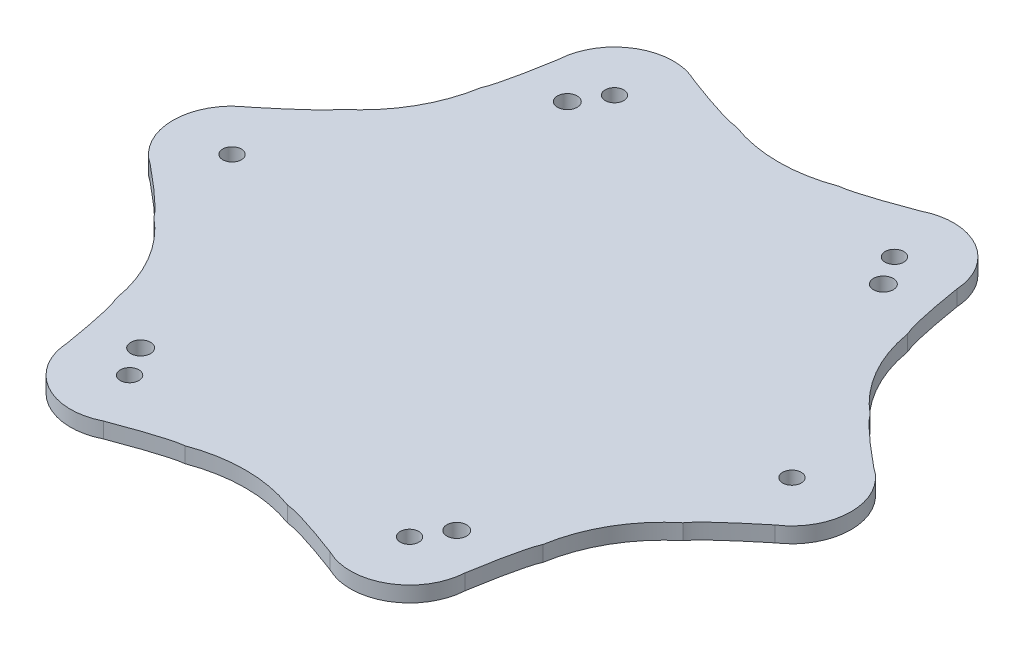
SolidWorks part; units mm, degrees
material "ABS"
ref_plane "Front" through (0, 0, 0) normal (0, 0, 1) x (1, 0, 0)
ref_plane "Top" through (0, 0, 0) normal (0, 1, 0) x (1, 0, 0)
ref_plane "Right" through (0, 0, 0) normal (1, 0, 0) x (0, 0, -1)
sketch "Sketch1" plane through (0, 0, 0) normal (0, 1, 0) x (1, 0, 0)
  line L0 (0, 45) -> (0, -45) construction
  line L1 (-45, 0) -> (45, 0) construction
  line L10 (0, 45) -> (0, 37.5) construction
  circle A0 centre (0, 0) radius 45
  dimension "D6" = 90
extrude "Boss-Extrude2" add sketch "Sketch1" along normal blind 2.5
ref_plane "Plane1" through (0, 2.5, 0) normal (0, 1, 0) x (1, 0, 0)
sketch "Sketch2" plane through (0, 2.5, 0) normal (0, 1, 0) x (1, 0, 0)
  line L0 (0, 45) -> (0, -45) construction
  line L1 (-45, 0) -> (45, 0) construction
  line L2 (-54.5, 0) -> (-35.5, 0) construction
  line L4 (-51.7175, -6.7175) -> (-45, 0) construction
  circle A0 centre (0, 0) radius 45 construction
  arc A2 (-42.2345, 15.532) -> (-42.2345, -15.532) centre (0, 0) ccw
  arc A3 (-50.2124, 7.9424) -> (-50.2124, -7.9424) centre (-45, 0) ccw
  spline S0 degree 3 poles (-50.2124, -7.9424) (-45.316, -11.9596) (-42.6567, -14.4895) (-42.2345, -15.532) knots 0.089312 0.089312 0.089312 0.089312 1 1 1 1
  spline S1 degree 3 poles (-50.2124, 7.9424) (-45.316, 11.9596) (-42.6567, 14.4895) (-42.2345, 15.532) knots 0.089312 0.089312 0.089312 0.089312 1 1 1 1
  dimension "D2" = 45
extrude "Boss-Extrude4" add sketch "Sketch2" against normal up to surface (2.5 mm away) up to face at (0, 0, 45)
pattern_circular "CirPattern1" count 6 over 360 about axis through (0, 2.5, 0) along (0, 1, 0) of "Boss-Extrude4"
ref_plane "Plane2" through (0, 2.5, 0) normal (0, 1, 0) x (1, 0, 0)
sketch "Sketch5" plane through (0, 2.5, 0) normal (0, 1, 0) x (1, 0, 0)
  line L0 (0, 45) -> (0, -45) construction
  line L1 (-8.2247, 44.3422) -> (0, 46.6578)
  line L2 (0, 46.6578) -> (8.2247, 44.3422)
  line L3 (40.4069, 23.3289) -> (42.5138, 15.0483)
  line L4 (34.2891, 29.2939) -> (40.4069, 23.3289)
  line L5 (40.4069, -23.3289) -> (34.2891, -29.2939)
  line L6 (42.5138, -15.0483) -> (40.4069, -23.3289)
  line L7 (0, -46.6578) -> (-8.2247, -44.3422)
  line L8 (8.2247, -44.3422) -> (0, -46.6578)
  line L9 (-40.4069, -23.3289) -> (-42.5138, -15.0483)
  line L10 (-34.2891, -29.2939) -> (-40.4069, -23.3289)
  line L11 (-40.4069, 23.3289) -> (-34.2891, 29.2939)
  line L12 (-42.5138, 15.0483) -> (-40.4069, 23.3289)
  arc A0 (7.6662, 44.3422) -> (-7.6662, 44.3422) centre (0, 0) ccw construction
  arc A1 (-7.6662, -44.3422) -> (7.6662, -44.3422) centre (0, 0) ccw construction
  arc A2 (-8.2247, 44.3422) -> (8.2247, 44.3422) centre (0, 66.2885) ccw
  arc A3 (34.2891, 29.2939) -> (42.5138, 15.0483) centre (57.4076, 33.1443) ccw
  arc A4 (42.5138, -15.0483) -> (34.2891, -29.2939) centre (57.4076, -33.1443) ccw
  arc A5 (8.2247, -44.3422) -> (-8.2247, -44.3422) centre (0, -66.2885) ccw
  arc A6 (-34.2891, -29.2939) -> (-42.5138, -15.0483) centre (-57.4076, -33.1443) ccw
  arc A7 (-42.5138, 15.0483) -> (-34.2891, 29.2939) centre (-57.4076, 33.1443) ccw
  parabola Q0 (-7.6662, 44.3422) -> (-18.2279, 47.4564) focus (-7.4049, 44.5798) apex (-7.3043, 44.5299) construction
  parabola Q1 (18.2279, 47.4564) -> (7.6662, 44.3422) focus (7.4049, 44.5798) apex (7.3043, 44.5299) construction
  point P42 (0, 0)
  dimension "D2" = 23.4369
  dimension "D1" = 6
extrude "Cut-Extrude2" cut sketch "Sketch5" against normal blind 2.5
ref_plane "Plane3" through (0, 2.5, 0) normal (0, 1, 0) x (1, 0, 0)
sketch "Sketch6" plane through (0, 2.5, 0) normal (0, 1, 0) x (1, 0, 0)
  line L0 (0, 42.8517) -> (0, -42.8517) construction
  circle A0 centre (-45, 0) radius 1.5
  arc A1 (-8.2247, 44.3422) -> (8.2247, 44.3422) centre (0, 66.2885) ccw construction
  arc A2 (8.2247, -44.3422) -> (-8.2247, -44.3422) centre (0, -66.2885) ccw construction
  circle A7 centre (-22.5, 38.9711) radius 1.5
  circle A8 centre (22.5, 38.9711) radius 1.5
  circle A9 centre (45, 0) radius 1.5
  circle A10 centre (22.5, -38.9711) radius 1.5
  circle A11 centre (-22.5, -38.9711) radius 1.5
  point P37 (0, 0)
  dimension "D4" = 3
  dimension "D5" = 22.5
  dimension "D3" = 6
extrude "Cut-Extrude3" cut sketch "Sketch6" against normal mid plane 10
sketch "Sketch7" plane through (0, 2.5, 0) normal (0, 1, 0) x (1, 0, 0)
  line L0 (0, 42.8517) -> (0, -42.8517) construction
  line L1 (-25.4, 34.29) -> (-25.4, -34.29) construction
  line L2 (-54.5, 0) -> (54.5, 0) construction
  line L3 (25.4, 34.29) -> (25.4, -34.29) construction
  arc A0 (-8.2247, 44.3422) -> (8.2247, 44.3422) centre (0, 66.2885) ccw construction
  arc A1 (8.2247, -44.3422) -> (-8.2247, -44.3422) centre (0, -66.2885) ccw construction
  circle A2 centre (-25.4, 34.29) radius 1.5875
  circle A3 centre (-25.4, -34.29) radius 1.5875
  arc A4 (-50.2124, 7.9424) -> (-50.2124, -7.9424) centre (-45, 0) ccw construction
  arc A5 (50.2124, -7.9424) -> (50.2124, 7.9424) centre (45, 0) ccw construction
  circle A6 centre (25.4, -34.29) radius 1.5875
  circle A7 centre (25.4, 34.29) radius 1.5875
  point P20 (-25.4, 0)
  point P25 (25.4, 0)
  dimension "D1" = 3.175
  dimension "D2" = 68.58
  dimension "D3" = 50.8
extrude "Cut-Extrude4" cut sketch "Sketch7" against normal up to surface (2.5 mm away) up to face at (-22.5, 0, 40.4711)
